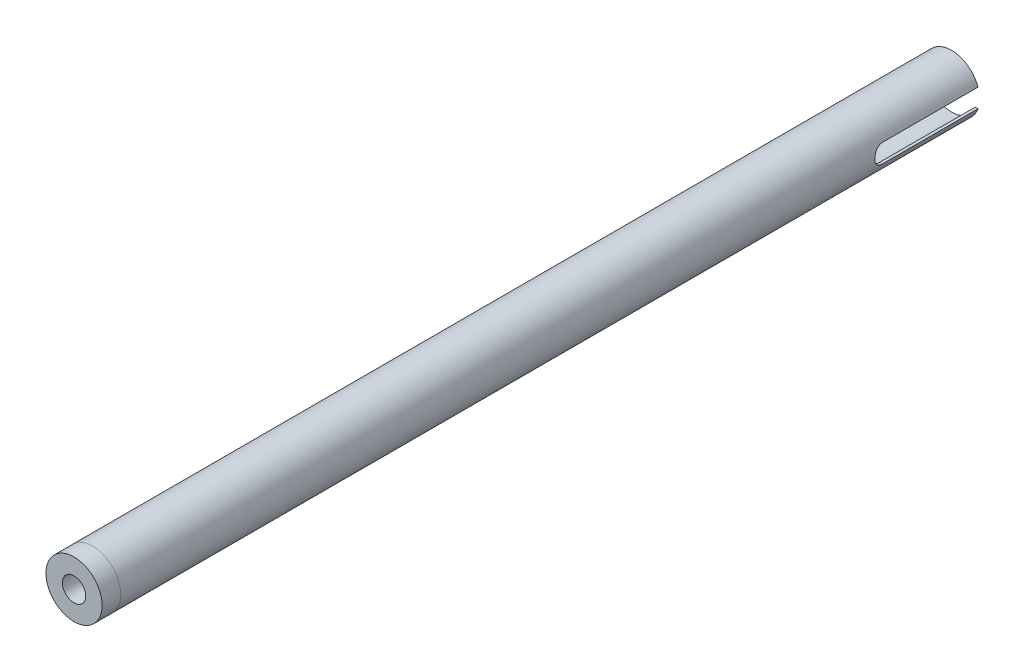
SolidWorks part; units mm, degrees
material "AISI 4130 Steel, normalized at 870C"
ref_plane "Front Plane" through (0, 0, 0) normal (0, 0, 1) x (1, 0, 0)
ref_plane "Top Plane" through (0, 0, 0) normal (0, 1, 0) x (1, 0, 0)
ref_plane "Right Plane" through (0, 0, 0) normal (1, 0, 0) x (0, 0, -1)
sketch "Axis" plane through (0, 0, 0) normal (0, 1, 0) x (1, 0, 0)
  line L0 (0, 0) -> (0, 297.7329) construction
  line L1 (0, 0) -> (0, -28.575) construction
  line L2 (0, 297.7329) -> (-9.525, 297.7329) construction
  line L3 (0, 325.6749) -> (-22.1529, 260.6884) construction
  dimension "D1" = 28.575
  dimension "D2" = 9.525
sketch "Sketch1" plane through (0, 0, 0) normal (0, 0, 1) x (1, 0, 0)
  line L0 (-9.525, 0) -> (9.525, 0) construction
  line L1 (-8.9803, 3.175) -> (8.9803, 3.175)
  line L2 (-8.9803, -3.175) -> (8.9803, -3.175)
  circle A0 centre (0, 0) radius 9.525
  circle A1 centre (0, 0) radius 8.636
  circle A2 centre (0, 0) radius 3.9688
  dimension "D1" = 19.05
  dimension "D3" = 7.9375
  dimension "D2" = 0.889
  dimension "D4" = 6.35
extrude "Threaded insert 1-1" add sketch "Sketch1" against normal blind 6.35 contours A2 L1 A1 | A1 L1 A0 | A2 L0 A1 L1 | A1 L0 A0 L1 | L0 A1 L2 A0 | L0 A2 L2 A1 | A2 L2 A1 | A1 L2 A0 | L0 A1 L2 A2 | L0 A0 L2 A1 | A0 L0 A1 L1 | A1 L0 A2 L1 region at (5.9465, 1.6355, 0) region at (5.9465, -1.6355, 0) region at (8.8881, 1.6046, 0) region at (8.8881, -1.6046, 0) region at (-5.9465, -1.6355, 0) region at (-5.9465, 1.6355, 0) region at (0, 5.5139, 0) region at (0, -5.5139, 0) region at (0, 8.8265, 0) region at (8.5057, -3.3655, 0) region at (-8.8881, -1.6046, 0) region at (-8.8881, 1.6046, 0)
extrude "Threaded insert 1-2" add sketch "Sketch1<3>" against normal blind 9.525 from surface contours A2 L1 A1 | A2 L0 A1 L1 | L0 A2 L2 A1 | A2 L2 A1 | L0 A1 L2 A2 | A1 L0 A2 L1 region at (5.9465, 1.6355, 0) region at (5.9465, -1.6355, 0) region at (-5.9465, -1.6355, 0) region at (-5.9465, 1.6355, 0) region at (0, 5.5139, 0) region at (0, -5.5139, 0) starting at face at (9.525, 0, -6.35)
sketch "Sketch1<3>" plane through (0, 0, 0) normal (0, 0, 1) x (1, 0, 0) same geometry as "Sketch1"
extrude "A-arm tube" add sketch "Sketch1<4>" against normal up to vertex (297.7329 mm away) from surface separate body contours A1 L1 A0 | A1 L0 A0 L1 | L0 A1 L2 A0 | A1 L2 A0 | L0 A0 L2 A1 | A0 L0 A1 L1 region at (8.8881, 1.6046, 0) region at (8.8881, -1.6046, 0) region at (0, 8.8265, 0) region at (8.5057, -3.3655, 0) region at (-8.8881, -1.6046, 0) region at (-8.8881, 1.6046, 0) up to point (0, 0, -297.7329) starting at face at (8.636, 0, -6.35)
sketch "Sketch1<4>" plane through (0, 0, 0) normal (0, 0, 1) x (1, 0, 0) same geometry as "Sketch1"
extrude "Apex slot" cut sketch "Sketch1<5>" along normal blind 35.56 from surface contours A0 L0 A1 L1 | L0 A0 L2 A1 | A1 L0 A0 L1 | L0 A1 L2 A0 region at (8.8881, 1.6046, 0) region at (8.8881, -1.6046, 0) region at (-8.8881, -1.6046, 0) region at (-8.8881, 1.6046, 0) starting at face at (8.636, 0, -297.7329)
sketch "Sketch1<5>" plane through (0, 0, 0) normal (0, 0, 1) x (1, 0, 0) same geometry as "Sketch1"
fillet "Fillet1" radius 3.175 4 edges at (-8.5057, 3.175, -262.1729) (-8.5057, -3.175, -262.1729) (8.5057, -3.175, -262.1729) (8.5057, 3.175, -262.1729)
equation "\"tube diameter\"= 3 / 4"
equation "\"tube thickness\"= .035"
equation "\"apex thickness\"= .25"
equation "\"tube slot\"= 1.4"
equation "\"D1@Sketch1\"=\"tube diameter\""
equation "\"D2@Sketch1\"=\"tube thickness\""
equation "\"threaded insert hole\"= .3125"
equation "\"D3@Sketch1\"=\"threaded insert hole\""
equation "\"D4@Sketch1\"=\"apex thickness\""
equation "\"D1@Apex slot\" = \"tube slot\""
equation "\"D1@Fillet1\"=\"apex thickness\"/2"
equation "\"D2@Axis\"=\"tube diameter\"/2"
